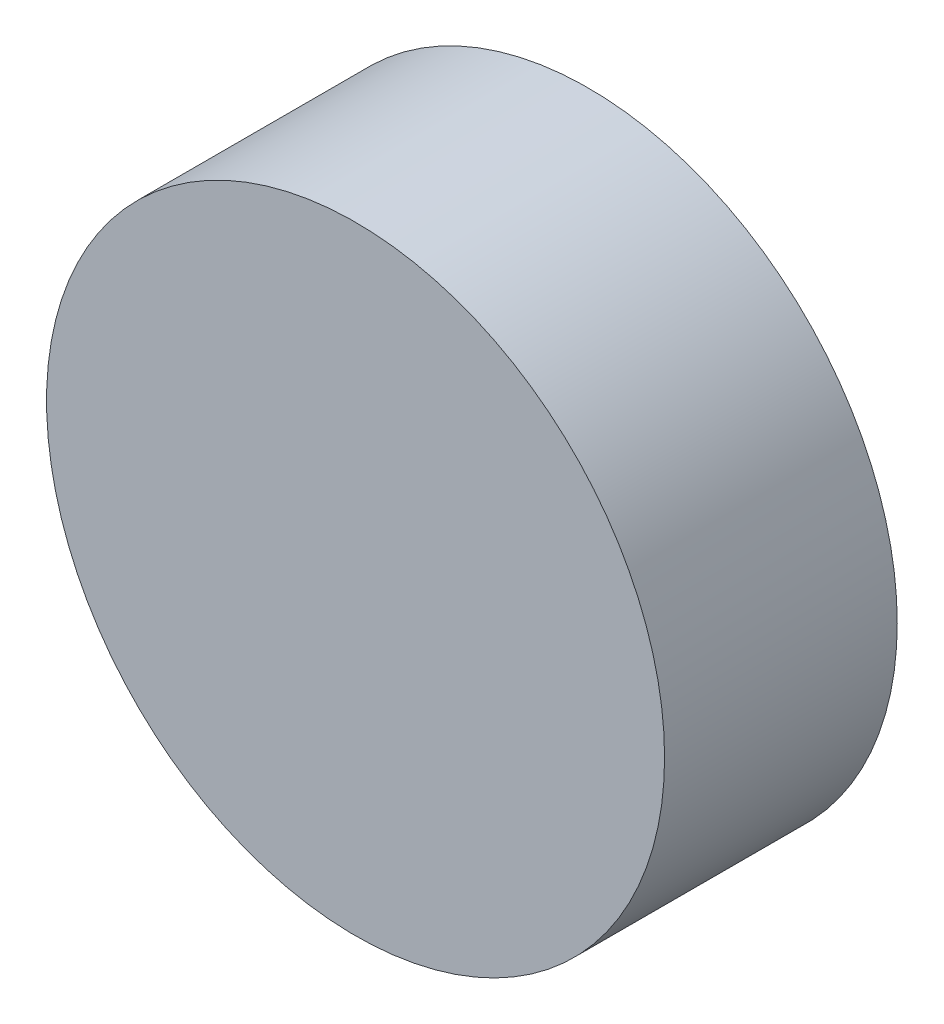
SolidWorks part; units mm, degrees
ref_plane "前视基准面" through (0, 0, 0) normal (0, 0, 1) x (1, 0, 0)
ref_plane "上视基准面" through (0, 0, 0) normal (0, 1, 0) x (1, 0, 0)
ref_plane "右视基准面" through (0, 0, 0) normal (1, 0, 0) x (0, 0, -1)
sketch "草图1" plane through (0, 0, 0) normal (0, 0, 1) x (1, 0, 0)
  circle A0 centre (0, 0) radius 42.5
  circle A1 centre (0, 0) radius 5.4
  dimension "D1" = 85
  dimension "D2" = 10.8
extrude "凸台-拉伸1" add sketch "草图1" along normal blind 32 contours A0
extrude "凸台-拉伸2" add sketch "草图1<3>" against normal blind 10 contours A1 region at (0, 0, 0)
sketch "草图1<3>" plane through (0, 0, 0) normal (0, 0, 1) x (1, 0, 0) same geometry as "草图1"
